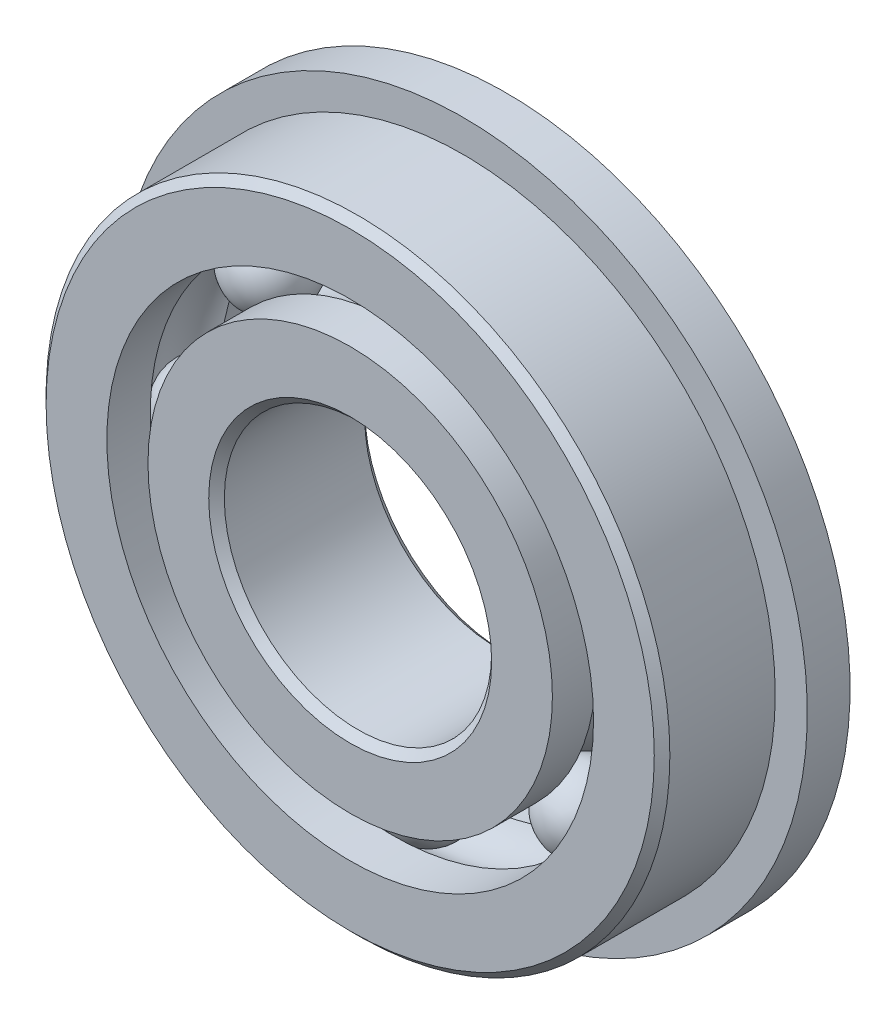
SolidWorks part; units mm, degrees
ref_plane "Front Plane" through (0, 0, 0) normal (0, 0, 1) x (1, 0, 0)
ref_plane "Top Plane" through (0, 0, 0) normal (0, 1, 0) x (1, 0, 0)
ref_plane "Right Plane" through (0, 0, 0) normal (1, 0, 0) x (0, 0, -1)
sketch "Sketch1" plane through (0, 0, 0) normal (1, 0, 0) x (0, 0, -1)
  line L0 (-2.7781, 0) -> (2.7781, 0) construction
  line L1 (0, 11.1125) -> (0, -11.1125) construction
  line L2 (2.5003, 11.1125) -> (-2.5003, 11.1125)
  line L3 (-2.5003, 11.1125) -> (-2.7781, 10.8347)
  line L4 (-2.7781, 10.8347) -> (-2.7781, 8.6702)
  line L5 (-2.7781, 8.6702) -> (-1.2347, 8.6702)
  line L6 (2.7781, 8.6702) -> (1.2347, 8.6702)
  line L7 (2.7781, 10.8347) -> (2.7781, 8.6702)
  line L8 (2.5003, 11.1125) -> (2.7781, 10.8347)
  line L9 (0, 11.1125) -> (0, 7.9375) construction
  line L10 (0, 7.9375) -> (0, 4.7625) construction
  arc A0 (-1.2347, 8.6702) -> (1.2347, 8.6702) centre (0, 7.9375) cw
  point P14 (0, 4.7625)
  dimension "Width" = 5.5562
  dimension "OD" = 22.225
  dimension "D1" = 45
  dimension "D2" = 0.2778
  dimension "Shaft Dia" = 9.525
  dimension "D3" = 2.4694
  dimension "D4" = 0.7327
revolve "Revolve1" add sketch "Sketch1" angle 360 about L0
sketch "Sketch3" plane through (0, 0, 0) normal (1, 0, 0) x (0, 0, -1)
  line L0 (-2.7781, 7.2048) -> (-1.2347, 7.2048)
  line L1 (0, 11.1125) -> (0, -11.1125) construction
  line L2 (-2.7781, 10.8347) -> (-2.7781, 8.6702) construction
  line L3 (-2.7781, 7.2048) -> (-2.7781, 5.0403)
  line L4 (-2.5003, 11.1125) -> (-2.7781, 10.8347) construction
  line L5 (-2.7781, 5.0403) -> (-2.5003, 4.7625)
  line L6 (-2.5003, 4.7625) -> (2.5003, 4.7625)
  line L7 (2.5003, 11.1125) -> (2.5003, -11.1125) construction
  line L8 (2.5003, 4.7625) -> (2.7781, 5.0403)
  line L9 (2.7781, -10.8347) -> (2.7781, 10.8347) construction
  line L10 (2.7781, 5.0403) -> (2.7781, 7.2048)
  line L11 (2.7781, 7.2048) -> (1.2347, 7.2048)
  line L13 (2.5003, 11.1125) -> (2.7781, 10.8347) construction
  arc A0 (1.2347, 8.6702) -> (-1.2347, 8.6702) centre (0, 7.9375) ccw construction
  arc A1 (1.2347, 7.2048) -> (-1.2347, 7.2048) centre (0, 7.9375) cw
revolve "Revolve3" add sketch "Sketch3" angle 360 about L0
sketch "Sketch4" plane through (0, 0, 0) normal (1, 0, 0) x (0, 0, -1)
  line L0 (-1.4357, 7.9375) -> (1.4357, 7.9375)
  arc A2 (-1.4357, 7.9375) -> (1.4357, 7.9375) centre (0, 7.9375) cw
  arc A3 (1.2347, 8.6702) -> (-1.2347, 8.6702) centre (0, 7.9375) ccw construction
revolve "Revolve4" add sketch "Sketch4" angle 360 about L0
ref_axis "Axis1" through (0, 0, -2.7781) along (0, 0, 1)
pattern_circular "CirPattern1" count 8 every 45 about axis through (0, 0, -2.7781) along (0, 0, 1) of bodies 104
sketch "Sketch6" plane through (0, 0, 0) normal (1, 0, 0) x (0, 0, -1)
  line L0 (2.7781, 0) -> (-2.7781, 0) construction
  line L1 (2.7781, 8.6702) -> (1.2541, 8.6702)
  line L2 (2.7781, 8.6702) -> (2.7781, 12.2555)
  line L3 (2.7781, 12.2555) -> (1.2541, 12.2555)
  line L4 (1.2541, 8.6702) -> (1.2541, 12.2555)
  dimension "Th" = 1.524
  dimension "Flange OD" = 24.511
revolve "Revolve6" add sketch "Sketch6" angle 360 about L0
equation "\"D2@Sketch1\" = \"Width@Sketch1\"*.05"
equation "\"D3@Sketch1\" = \"Width@Sketch1\"/2.25"
equation "\"D4@Sketch1\" = (((\"OD@Sketch1\"-\"Width@Sketch1\")/2)/3.25)/3.5"
equation "\"D2@CirPattern1\" = 360/\"Balls@CirPattern1\""
